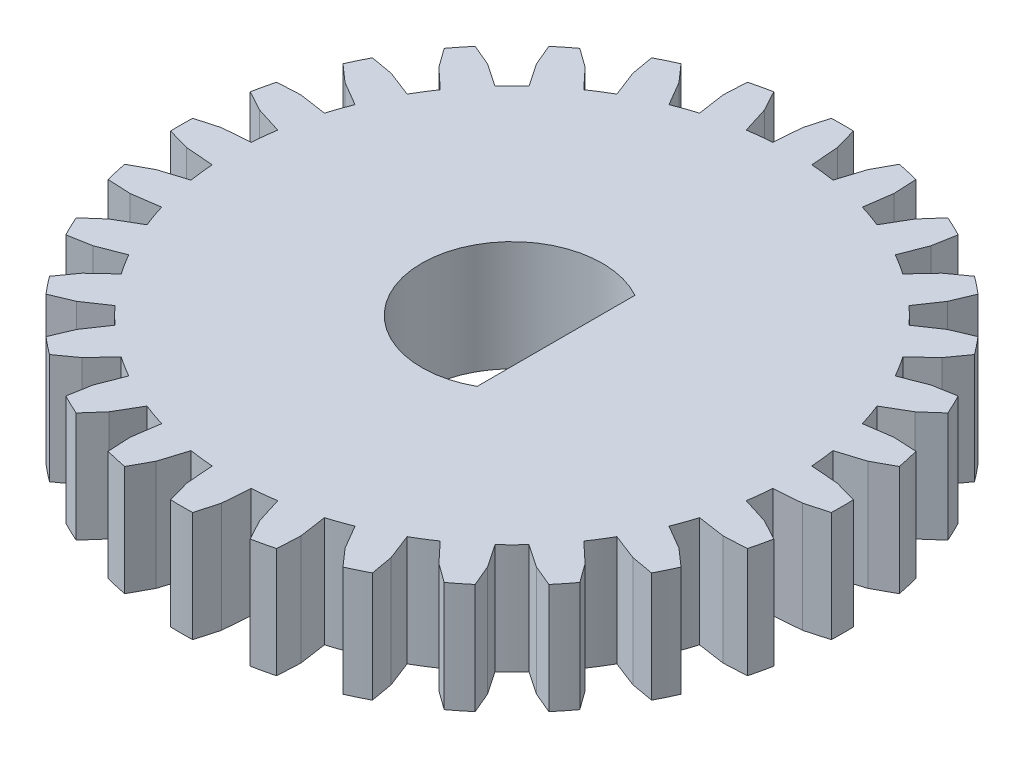
SolidWorks part; units mm, degrees
ref_plane "Front Plane" through (0, 0, 0) normal (0, 0, 1) x (1, 0, 0)
ref_plane "Top Plane" through (0, 0, 0) normal (0, 1, 0) x (1, 0, 0)
ref_plane "Right Plane" through (0, 0, 0) normal (1, 0, 0) x (0, 0, -1)
sketch "Sketch1" plane through (0, 0, 0) normal (0, 1, 0) x (1, 0, 0)
  line L0 (0, -33.7354) -> (0, 33.7354) construction
  line L1 (0.785, 13.978) -> (0.885, 12.7192)
  line L2 (0.785, 13.978) -> (0.5, 14.9917)
  line L3 (-0.785, 13.978) -> (-0.5, 14.9917)
  line L4 (-0.785, 13.978) -> (-0.885, 12.7192)
  line L5 (2, 3.5791) -> (2, -3.5791)
  circle A0 centre (0, 0) radius 14 construction
  arc A1 (0.5, 14.9917) -> (-0.5, 14.9917) centre (0, 0) ccw
  circle A2 centre (0, 0) radius 12.75
  arc A3 (2, 3.5791) -> (2, -3.5791) centre (0, 0) ccw
  point P6 (0.785, 13.978)
  point P11 (0, 0)
  dimension "D1" = 28
  dimension "D2" = 30
  dimension "D3" = 25.5
  dimension "D7" = 8.2
  dimension "D4" = 0.785
  dimension "D5" = 0.5
  dimension "D6" = 0.885
  dimension "D8" = 2
extrude "Boss-Extrude1" add sketch "Sketch1" along normal blind 5 contours A2 | A2 L1 L2 A1 L4 L3 region at (0, 0, -13.7743) region at (9.0596, 0, -8.4511)
pattern_circular "CirPattern2" count 28 over 360 about axis through (0, 5, 0) along (0, 1, 0) of face at (-0.835, 2.5, -13.3486) of face at (0.835, 2.5, -13.3486) of face at (0.6425, 2.5, -14.4848) of face at (0, 2.5, -14.9958) of face at (-0.6425, 2.5, -14.4848)
sketch "Sketch2" plane through (0, 0, 0) normal (1, 0, 0) x (0, 0, -1)
  line L0 (0, -12.9244) -> (0, 12.9244) construction
  point P4 (0, 0)
